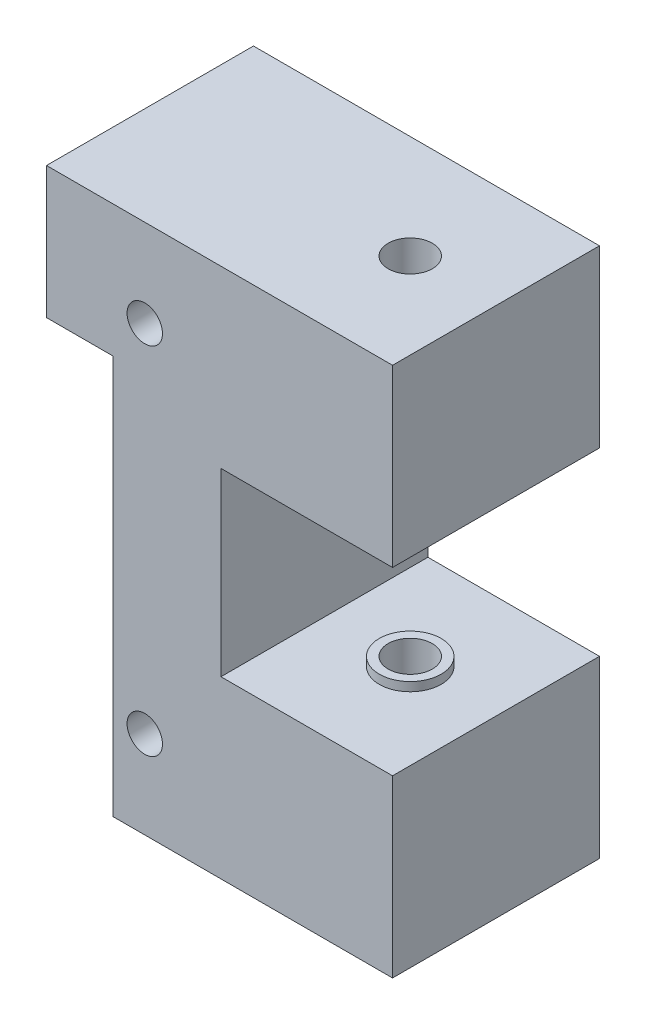
SolidWorks part; units mm, degrees
ref_plane "Front Plane" through (0, 0, 0) normal (0, 0, 1) x (1, 0, 0)
ref_plane "Top Plane" through (0, 0, 0) normal (0, 1, 0) x (1, 0, 0)
ref_plane "Right Plane" through (0, 0, 0) normal (1, 0, 0) x (0, 0, -1)
sketch "MainBlock" plane through (0, 0, 0) normal (0, 0, 1) x (1, 0, 0)
  line L0 (0, 0) -> (39.125, 0)
  line L1 (39.125, 0) -> (39.125, 19.8)
  line L2 (39.125, 19.8) -> (19.725, 19.8)
  line L3 (19.725, 19.8) -> (19.725, 40.2)
  line L4 (19.725, 40.2) -> (39.125, 40.2)
  line L5 (39.125, 40.2) -> (39.125, 60)
  line L6 (39.125, 60) -> (0, 60)
  line L7 (0, 60) -> (0, 0)
  circle A0 centre (11.1125, 50.1) radius 2
  circle A1 centre (11.1125, 9.9) radius 2
  dimension "D4" = 4
  dimension "D1" = 39.125
  dimension "D2" = 60
  dimension "D3" = 20.4
  dimension "D5" = 19.4
  dimension "D6" = 11.1125
  dimension "D7" = 9.9
  dimension "D8" = 9.9
  dimension "D9" = 19.8
  dimension "D10" = 19.8
extrude "MainBlockBoss-Extrude1" add sketch "MainBlock" along normal blind 23.4
sketch "TopHoleCut-Sketch2" plane through (0, 60, 0) normal (0, 1, 0) x (1, 0, 0)
  line L0 (39.125, 0) -> (0, 0) construction
  circle A0 centre (29.425, -11.7) radius 2.5
  dimension "D3" = 5
  dimension "D1" = 11.7
  dimension "D2" = 9.7
extrude "TopHoleCut-Extrude1" cut sketch "TopHoleCut-Sketch2" against normal blind 45
sketch "TopSpacerSketch4" plane through (0, 40.2, 0) normal (0, -1, 0) x (1, 0, 0)
  circle A0 centre (29.425, 11.7) radius 3.5
  circle A1 centre (29.425, 11.7) radius 2.5
  circle A2 centre (29.425, 11.7) radius 2.5 construction
  dimension "D1" = 7
extrude "TopSpacerBoss-Extrude2" add sketch "TopSpacerSketch4" along normal blind 1
sketch "LowerSpacerSketch5" plane through (0, 19.8, 0) normal (0, 1, 0) x (1, 0, 0)
  circle A0 centre (29.425, -11.7) radius 2.5
  circle A1 centre (29.425, -11.7) radius 2.5 construction
  circle A2 centre (29.425, -11.7) radius 3.5
  circle A3 centre (29.425, -11.7) radius 3.5 construction
extrude "LowerSpacerBoss-Extrude3" add sketch "LowerSpacerSketch5" along normal blind 1
sketch "MountHoleBoreSketch1" plane through (0, 0, 0) normal (0, 0, -1) x (-1, 0, 0)
  line L1 (-7.2375, 50.1) -> (-9.175, 53.4558)
  line L2 (-9.175, 53.4558) -> (-13.05, 53.4558)
  line L3 (-13.05, 53.4558) -> (-14.9875, 50.1)
  line L4 (-14.9875, 50.1) -> (-13.05, 46.7442)
  line L5 (-13.05, 46.7442) -> (-9.175, 46.7442)
  line L6 (-9.175, 46.7442) -> (-7.2375, 50.1)
  line L7 (-7.2375, 9.9) -> (-9.175, 13.2558)
  line L8 (-9.175, 13.2558) -> (-13.05, 13.2558)
  line L9 (-13.05, 13.2558) -> (-14.9875, 9.9)
  line L10 (-14.9875, 9.9) -> (-13.05, 6.5442)
  line L11 (-13.05, 6.5442) -> (-9.175, 6.5442)
  line L12 (-9.175, 6.5442) -> (-7.2375, 9.9)
  circle A0 centre (-11.1125, 50.1) radius 3.3558 construction
  circle A1 centre (-11.1125, 9.9) radius 3.3558 construction
  dimension "D1" = 7.75
extrude "MountHoleBoreCut-Extrude1" cut sketch "MountHoleBoreSketch1" against normal blind 2
sketch "PushPinHoleSketch1" plane through (0, 0, 0) normal (0, -1, 0) x (1, 0, 0)
  circle A0 centre (29.425, 11.7) radius 1
  circle A1 centre (29.425, 11.7) radius 2.5 construction
  dimension "D1" = 2
extrude "PushPinHoleCut-Extrude1" cut sketch "PushPinHoleSketch1" against normal through all
sketch "MidRailInsetSketch1" plane through (0, 0, 0) normal (0, 0, -1) x (-1, 0, 0)
  line L0 (0, 60) -> (0, 0) construction
  line L1 (0, 45.1) -> (-7.5, 45.1)
  line L2 (0, 45.1) -> (0, 0)
  line L3 (0, 0) -> (-7.5, 0)
  line L4 (-7.5, 45.1) -> (-7.5, 0)
  line L6 (0, 0) -> (-39.125, 0) construction
  line L7 (-39.125, 60) -> (0, 60) construction
  dimension "D1" = 7.5
  dimension "D2" = 14.9
extrude "MidRailInsetCut-Extrude2" cut sketch "MidRailInsetSketch1" against normal through all
equation "\"BeltTensionerWidth\"= \"MidRailToAlignWithGantryBlock\" + \"BeltTensionerInnerWidth\" / 2 + \"RailThickness\""
equation "\"BeltTensionerHeight\"= 60mm"
equation "\"BeltTensionerDepth\"= \"BeltTensionerBackWallThickness\" + \"BeltTensionerInnerDepth\"'Equals 23.4"
equation "\"BeltTensionerInnerWidth\"= \"20TGT2PulleyDiameter\" + \"BeltTensionerSpaceBetweenPulleyAndWall\""
equation "\"BeltTensionerInnerHeight\"= \"20TGT2PulleyWidth\" * 2 + \"1mmSpacer\" * 3"
equation "\"BeltTensionerBackWallThickness\"= 4mm"
equation "\"BeltTensionerInnerDepth\"= \"20TGT2PulleyDiameter\" + \"BeltTensionerSpaceBetweenPulleyAndWall\""
equation "\"RailThickness\"= .125in'Spec"
equation "\"HoleOffsetFromEdge\"= \"RailThickness\" * 2.5"
equation "\"LinearGBWithRailDepth\"= 12.75mm'Spec"
equation "\"GABDistanceFromBackToFirstPulley\"= 13.5mm"
equation "\"MidRailToAlignWithGantryBlock\"= \"LinearGBWithRailDepth\" + \"GABDistanceFromBackToFirstPulley\"'All outside cogs must align"
equation "\"20TGT2PulleyDiameter\"= 17.9mm'Spec"
equation "\"BeltTensionerSpaceBetweenPulleyAndWall\"= 1.5mm"
equation "\"BeltTensionerMountingHoleDiameter\"= 4.0mm"
equation "\"BeltTensionerMountingHoleOffsetFromEdge\"= \"HoleOffsetFromEdge\""
equation "\"20TGT2PulleyWidth\"= 8.7mm'The STL of the Pulley in the diagram is a bit larger"
equation "\"1mmSpacer\"= 1mm"
equation "\"SteelShaft5mmHoleDiameter\"= 5mm"
equation "\"BeltTensionerMountingHoleOuterBoreDepth\"= 2mm"
equation "\"BeltTensionerMountingHoleOuterBoreDiameter\"= 7.75mm"
equation "\"7mmx1mmSpacerDiameter\"= 7mm"
equation "\"7mmx1mmSpacerHeight\"= 1mm"
equation "\"D1@MainBlock\" = \"BeltTensionerWidth\""
equation "\"D4@MainBlock\" = \"BeltTensionerMountingHoleDiameter\""
equation "\"D5@MainBlock\" = \"BeltTensionerInnerWidth\""
equation "\"D6@MainBlock\"=\"BeltTensionerMountingHoleOffsetFromEdge\" + \"RailThickness\""
equation "\"D7@MainBlock\"=\"BeltTensionerMountingHoleOffstFromTopOrBottom\""
equation "\"D8@MainBlock\"=\"BeltTensionerMountingHoleOffstFromTopOrBottom\""
equation "\"D1@MainBlockBoss-Extrude1\" = \"BeltTensionerDepth\""
equation "\"D1@TopHoleCut-Sketch2\" = \"BeltTensionerDepth\" / 2"
equation "\"D3@TopHoleCut-Sketch2\" = \"SteelShaft5mmHoleDiameter\""
equation "\"D1@TopSpacerSketch4\" = \"7mmx1mmSpacerDiameter\""
equation "\"D1@TopSpacerBoss-Extrude2\" = \"7mmx1mmSpacerHeight\""
equation "\"D1@LowerSpacerBoss-Extrude3\" = \"7mmx1mmSpacerHeight\""
equation "\"D1@MountHoleBoreSketch1\" = \"BeltTensionerMountingHoleOuterBoreDiameter\""
equation "\"D1@MountHoleBoreCut-Extrude1\" = \"BeltTensionerMountingHoleOuterBoreDepth\""
equation "\"SteelPinPushHoleDiameter\"= 2mm"
equation "\"D1@PushPinHoleSketch1\" = \"SteelPinPushHoleDiameter\""
equation "\"D2@TopHoleCut-Sketch2\"=\"BeltTensionerWidth\" - \"MidRailToAlignWithGantryBlock\" - \"RailThickness\""
equation "\"BeltTensionerMountingHoleOffstFromTopOrBottom\"= ( \"BeltTensionerHeight\" - \"BeltTensionerInnerHeight\" ) / 4"
equation "\"BeltTensionerSteelShaftHoleDepthFromTop\"= ( \"SteelShaftLength\" - \"BeltTensionerInnerHeight\" ) / 2 + ( \"BeltTensionerHeight\" - \"BeltTensionerInnerHeight\" ) / 2 + \"BeltTensionerInnerHeight\"'Equals 45"
equation "\"SteelShaftLength\"= 30mm"
equation "\"D1@TopHoleCut-Extrude1\"=\"BeltTensionerSteelShaftHoleDepthFromTop\""
equation "\"MidSideRailVerticalOffset\"= \"LinearRailWidth\" + 3mm'Allows space for RodStabilizer to attach to bottom of MidSideRail"
equation "\"LinearRailWidth\"= 12mm'Spec"
equation "\"D2@MidRailInsetSketch1\"=\"DistanceAboveMidSideRailToTopOfBeltTensioner\""
equation "\"DistanceAboveMidSideRailToTopOfBeltTensioner\"= \"VS ToTopOfBeltTensionerAlignedWithYAxisGantryBlockUpperPulley\" - \"V8 ToTopOfMidSideRail\"'Equals 14.9"
equation "\"DistanceFromBeltTensionerTopPulleyToBeltTensionerTop\"= \"7mmx1mmSpacerHeight\" + \"BeltTensionerTopHeight\"'Equals 20.8"
equation "\"BeltTensionerTopHeight\"= ( \"BeltTensionerHeight\" - \"BeltTensionerInnerHeight\" ) / 2'Equals 19.8"
equation "\"GABUpperHeight\"= 4mm"
equation "\"D3@MainBlock\"=\"BeltTensionerInnerHeight\""
equation "\"D9@MainBlock\"=\"BeltTensionerTopHeight\""
equation "\"LegHeight\"= 70mm'Space needed for PSU/Stepper/Electronics"
equation "\"V1 BottomOfLowerRail\"= \"LegHeight\""
equation "\"LowerEnclosureThickness\"= 5mm"
equation "\"StepperShaftLength\"= 24mm'Pulley will be attached to the end"
equation "\"ZAxisLeadScrewLength\"= 200mm"
equation "\"LM8UUHeight\"= 24mm'Spec"
equation "\"V2 ToBedAtTopOfZAxis\"= \"V1 BottomOfLowerRail\" - \"LowerEnclosureThickness\" + \"StepperShaftLength\" + \"ZAxisLeadScrewLength\" - \"LM8UUHeight\" / 2'Equals 277"
equation "\"BedToBuildPlateStandoffLength\"= 15mm"
equation "\"BuildPlateHeight\"= 8mm'Spec"
equation "\"V4 ToTopOfBuildPlate/HotEndTip\"= \"V2 ToBedAtTopOfZAxis\" + \"BedToBuildPlateStandoffLength\" + \"BuildPlateHeight\""
equation "\"HotEndToTopOfXAxisGB\"= 71.68487mm'Equals 71.68487. Measured after installed onto X-Axis linear rail guide block"
equation "\"LinearGBWidth\"= 27mm'Spec"
equation "\"TopOfGBToBottomOfLinearRail\"= \"LinearGBWidth\" / 2 + \"LinearRailWidth\" / 2'Equals 19.5"
equation "\"V5 ToBottomOfXAxisLinearRail\"= \"V4 ToTopOfBuildPlate/HotEndTip\" + \"HotEndToTopOfXAxisGB\" - \"TopOfGBToBottomOfLinearRail\"'Equals 352.18487"
equation "\"GABMidWallHeight\"= 28mm'Must equal 28 or changes alignment"
equation "\"GABLowerHeight\"= 4mm"
equation "\"GABHeight\"= \"GABLowerHeight\" + \"GABMidWallHeight\" + \"GABUpperHeight\""
equation "\"V6 ToMiddleOfYAxisGantryBlock\"= \"V5 ToBottomOfXAxisLinearRail\" - \"GABHeight\" / 2'Equals 334.18487"
equation "\"V8 ToTopOfMidSideRail\"= \"V6 ToMiddleOfYAxisGantryBlock\" + \"MidSideRailVerticalOffset\"'Equals 349.18487"
equation "\"VS ToTopOfBeltTensionerAlignedWithYAxisGantryBlockUpperPulley\"= \"V5 ToBottomOfXAxisLinearRail\" - \"DistanceFromXAxisLinearRailBottomAndTopOfGantryPulley\" + \"DistanceFromBeltTensionerTopPulleyToBeltTensionerTop\"'Equals 364.08487"
equation "\"GABRiserBossOffset\"= 0.4mm'Aligns Pulleys inside edges to be 2.5mm (.5mm apart top to bottom)"
equation "\"GABMidShortRiserHeight\"= \"GABMidWallHeight\" / 2 - \"20TGT2PulleyWidth\"'Equals 5.3"
equation "\"DistanceFromXAxisLinearRailBottomAndTopOfGantryPulley\"= \"GABUpperHeight\" + \"GABMidShortRiserHeight\" - \"GABRiserBossOffset\"'Equals 8.9"
